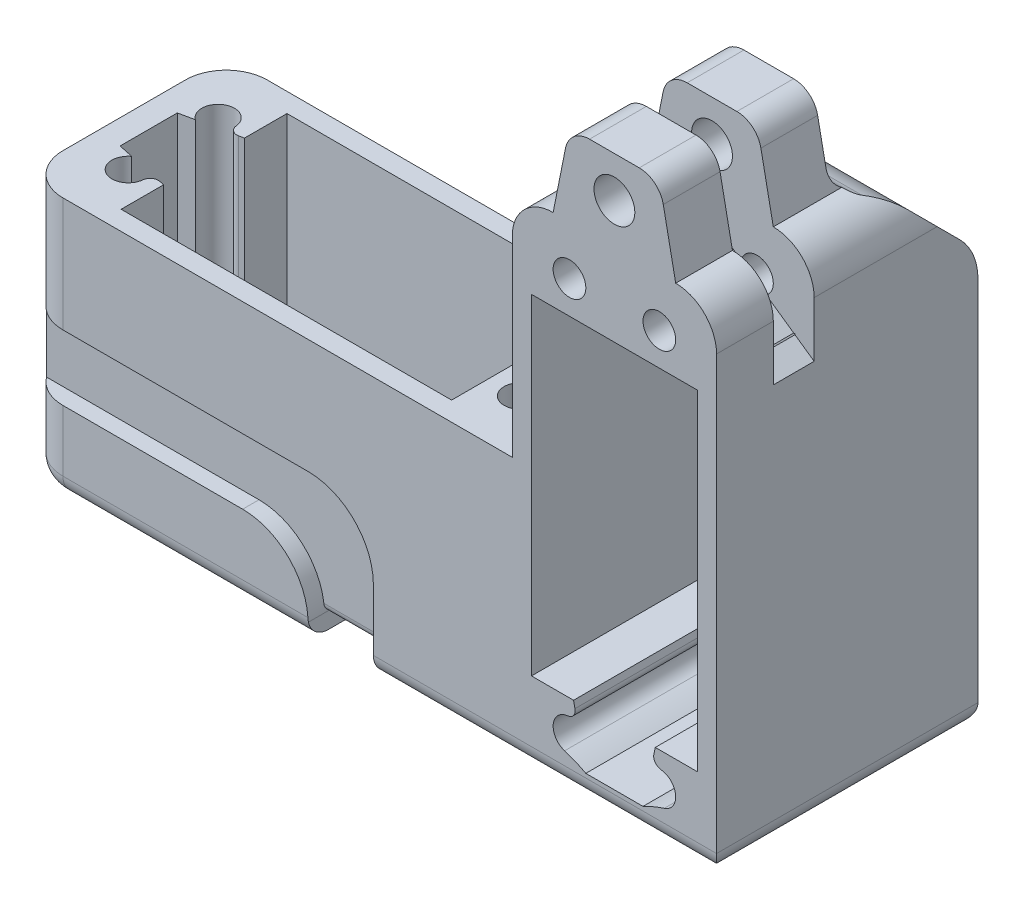
SolidWorks part; units mm, degrees
note: The reader was unsure of these and kept them because the rebuilt part matched: shared geometry of "Croquis3<2>", "Croquis9<3>".
ref_plane "Alzado" through (0, 0, 0) normal (0, 0, 1) x (1, 0, 0)
ref_plane "Planta" through (0, 0, 0) normal (0, 1, 0) x (1, 0, 0)
ref_plane "Vista lateral" through (0, 0, 0) normal (1, 0, 0) x (0, 0, -1)
sketch "Croquis1" plane through (0, 0, 0) normal (0, 0, 1) x (1, 0, 0)
  line L0 (-10, 40) -> (-10, 0) construction
  line L3 (-20, 40) -> (20, 40) construction
  line L4 (-20, 40) -> (-20, 0) construction
  line L5 (-20, 0) -> (20, 0) construction
  line L6 (20, 40) -> (20, 0) construction
  line L7 (-27, 28) -> (-27, 30.5) construction
  line L8 (-27, 30.5) -> (-20, 30.5) construction
  line L9 (-27, 28) -> (-20, 28) construction
  line L10 (27, 28) -> (27, 30.5) construction
  line L11 (27, 30.5) -> (20, 30.5) construction
  line L12 (27, 28) -> (20, 28) construction
  line L13 (-14.4, 40) -> (-14.4, 43.2) construction
  line L14 (-14.4, 43.2) -> (-5.6, 43.2) construction
  line L15 (-5.6, 43.2) -> (-5.6, 40) construction
  line L16 (-14.4, 43.2) -> (-20, 43.2) construction
  line L17 (-20, 43.2) -> (-20, 45.5) construction
  line L18 (-20, 45.5) -> (0, 45.5) construction
  line L19 (0, 45.5) -> (0, 43.2) construction
  line L20 (0, 43.2) -> (-5.6, 43.2) construction
  point P0 (0, 0)
  point P20 (-10, 43.2)
  point P27 (-10, 45.5)
  dimension "D1" = 40
  dimension "D2" = 40
  dimension "D4" = 10
  dimension "D5" = 7
  dimension "D6" = 2.5
  dimension "D7" = 9.5
  dimension "D9" = 8.8
  dimension "D10" = 20
  dimension "D11" = 2.3
  dimension "D12" = 3.2
sketch "Croquis2" plane through (0, 0, 0) normal (0, 1, 0) x (1, 0, 0)
  line L1 (-20, 10) -> (-27, 10) construction
  line L2 (-20, 10) -> (-20, -10) construction
  line L3 (-20, -10) -> (-27, -10) construction
  line L4 (-27, 10) -> (-27, -10) construction
  line L8 (-27, 10.15) -> (-20, 10.15) construction
  line L9 (-20, 10.15) -> (-20, 10) construction
  line L10 (-27, 10.15) -> (-27, 10) construction
  line L11 (-55, 0) -> (55, 0) construction
  line L12 (-20, -10.15) -> (-20, -10) construction
  line L13 (-27, -10.15) -> (-20, -10.15) construction
  line L14 (-27, -10.15) -> (-27, -10) construction
  circle A0 centre (-24, 5.5) radius 2 construction
  point P4 (-20, 0)
  dimension "D4" = 4
  dimension "D1" = 20
  dimension "D2" = 7
  dimension "D3" = 3
  dimension "D5" = 4.5
  dimension "D6" = 0.15
sketch "Croquis3" plane through (0, 0, 0) normal (0, 1, 0) x (1, 0, 0)
  line L1 (-20, -12.5) -> (-25, -12.5)
  line L3 (-20, 12.5) -> (-25, 12.5)
  line L4 (-30, -7.5) -> (-30, 7.5)
  line L5 (-20, 12.5) -> (20, 12.5)
  line L6 (-20, -12.5) -> (20, -12.5)
  line L7 (-20.225, 10.15) -> (20.225, 10.15)
  line L8 (-20.225, -10.15) -> (20.225, -10.15)
  line L9 (-20.225, 10.15) -> (-20.225, -10.15)
  line L10 (-55, 0) -> (55, 0) construction
  line L11 (0, -55) -> (0, 55) construction
  line L12 (-20, 10) -> (-20, -10) construction
  line L13 (20.225, 10.15) -> (20.225, -10.15)
  line L15 (20, 12.5) -> (25, 12.5)
  line L16 (20, -12.5) -> (25, -12.5)
  line L17 (-27, 10.15) -> (-20, 10.15) construction
  line L18 (-27, -10.15) -> (-20, -10.15) construction
  line L19 (25, 12.5) -> (30, 12.5)
  line L20 (30, 12.5) -> (30, -12.5)
  line L21 (30, -12.5) -> (25, -12.5)
  arc A0 (-25, -12.5) -> (-30, -7.5) centre (-25, -7.5) cw
  arc A1 (-30, 7.5) -> (-25, 12.5) centre (-25, 7.5) cw
  circle A2 centre (-24, 5.5) radius 2 construction
  circle A3 centre (-24, 5.5) radius 2
  circle A4 centre (-24, -5.5) radius 2
  circle A5 centre (24, -5.5) radius 2
  circle A6 centre (24, 5.5) radius 2
  point P6 (-30, 0)
  point P9 (30, 12.5)
  point P10 (0, 12.5)
  point P11 (0, -12.5)
  point P14 (0, 10.15)
  point P20 (-30, -12.5)
  point P23 (-30, 12.5)
  point P47 (0, -10.15)
  point P48 (30, -12.5)
  dimension "D3" = 5
  dimension "D1" = 10
  dimension "D2" = 25
  dimension "D4" = 0.225
  dimension "D5" = 0.225
extrude "Saliente-Extruir1" add sketch "Croquis3" along normal up to vertex (28 mm away) up to point (-20, 28, 0)
extrude "Saliente-Extruir2" add sketch "Croquis3<2>" against normal blind 4
sketch "Croquis3<2>" plane through (0, 0, 0) normal (0, 1, 0) x (1, 0, 0) same geometry as "Croquis3"
sketch "Croquis4" plane through (0, 28, 0) normal (0, 1, 0) x (1, 0, 0)
  line L0 (-20, 5) -> (-20, -5)
  line L1 (-20, 10) -> (-20, -10) construction
  line L2 (-20, -5) -> (-27, -3.5)
  line L3 (-27, -3.5) -> (-27, 3.5)
  line L4 (-27, 3.5) -> (-20, 5)
  point P4 (-20, 0)
  dimension "D1" = 7
  dimension "D2" = 10
  dimension "D3" = 7
extrude "Cortar-Extruir1" cut sketch "Croquis4" against normal offset from surface (23 mm away) 5 up to face at (0, 0, 0)
fillet "Redondeo12" radius 1 2 edges at (-22.2588, 16.5, 4.516) (-22.2588, 16.5, -4.516)
sketch "Croquis5" plane through (-20.225, 0, 0) normal (1, 0, 0) x (0, 0, -1)
  line L0 (4.9518, 5) -> (-4.9518, 5) construction
  line L1 (-4.9518, 5) -> (4.9518, 5)
  line L2 (-4.9518, 5) -> (-4.9518, 9)
  line L3 (-4.9518, 9) -> (4.9518, 9)
  line L4 (4.9518, 5) -> (4.9518, 9)
  dimension "D1" = 4
extrude "Cortar-Extruir2" cut sketch "Croquis5" against normal through all
sketch "Croquis6" plane through (0, -4, 0) normal (0, -1, 0) x (1, 0, 0)
  line L0 (-20, 0) -> (0, 0) construction
  circle A0 centre (-10, 0) radius 8.125
  dimension "D1" = 16.25
extrude "Cortar-Extruir3" cut sketch "Croquis6" against normal blind 4
fillet "Redondeo4" radius 5 1 edges at (-27, 9, 0)
sketch3d "Croquis3D4"
  point P0 (30, 6.8279, 1.7662)
ref_plane "Plano1" through (30, 0, 0) normal (1, 0, 0) x (0, 1, 0)
sketch "Croquis7" plane through (30, 0, 0) normal (1, 0, 0) x (0, 1, 0)
  line L0 (16, 24.5) -> (16, -15.5) construction
  line L3 (6, 24.5) -> (46, 24.5) construction
  line L4 (6, 24.5) -> (6, -15.5) construction
  line L5 (6, -15.5) -> (46, -15.5) construction
  line L6 (46, 24.5) -> (46, -15.5) construction
  line L7 (-1, 12.5) -> (-1, 15) construction
  line L8 (-1, 15) -> (6, 15) construction
  line L9 (-1, 12.5) -> (6, 12.5) construction
  line L10 (53, 12.5) -> (53, 15) construction
  line L11 (53, 15) -> (46, 15) construction
  line L12 (53, 12.5) -> (46, 12.5) construction
  line L13 (11.6, 24.5) -> (11.6, 27.7) construction
  line L14 (11.6, 27.7) -> (20.4, 27.7) construction
  line L15 (20.4, 27.7) -> (20.4, 24.5) construction
  line L16 (11.6, 27.7) -> (6, 27.7) construction
  line L17 (6, 27.7) -> (6, 30) construction
  line L18 (6, 30) -> (26, 30) construction
  line L19 (26, 30) -> (26, 27.7) construction
  line L20 (26, 27.7) -> (20.4, 27.7) construction
  point P20 (16, 27.7)
  point P27 (16, 30)
  dimension "D1" = 40
  dimension "D2" = 40
  dimension "D3" = 1
  dimension "D4" = 10
  dimension "D5" = 7
  dimension "D6" = 2.5
  dimension "D7" = 9.5
  dimension "D8" = 24.5
  dimension "D9" = 8.8
  dimension "D10" = 20
  dimension "D11" = 2.3
  dimension "D12" = 3.2
sketch3d "Croquis3D5"
  point P0 (-4.4818, 17.5523, 12.5)
ref_plane "Plano2" through (0, 0, 12.5) normal (0, 0, 1) x (0, 1, 0)
sketch "Croquis9" plane through (0, 0, 12.5) normal (0, 0, 1) x (0, 1, 0)
  line L0 (6, -55) -> (1, -55)
  line L1 (6, -55) -> (6, -30) construction
  line L2 (6, -30) -> (1, -30)
  line L3 (-4, -50) -> (-4, -35)
  line L4 (6, -30) -> (46.45, -30)
  line L5 (6, -55) -> (46.45, -55)
  line L6 (6, -32.35) -> (46.45, -32.35)
  line L7 (6, -52.65) -> (46.45, -52.65)
  line L8 (6, -32.35) -> (6, -52.65)
  line L9 (-4, -35) -> (-4, -30)
  line L10 (26.225, -60.6027) -> (26.225, -26.5509) construction
  line L11 (46.45, -55) -> (51.45, -55)
  line L12 (46.45, -30) -> (51.45, -30)
  line L13 (56.45, -50) -> (56.45, -35)
  line L14 (46.45, -32.35) -> (46.45, -52.65)
  line L15 (28, -30) -> (-4, -30) construction
  line L16 (-4, -30) -> (1, -30)
  line L17 (-4, -50) -> (-4, -55)
  line L18 (-4, -55) -> (1, -55)
  circle A2 centre (2, -37) radius 2
  circle A3 centre (2, -48) radius 2
  arc A4 (51.45, -55) -> (56.45, -50) centre (51.45, -50) ccw
  arc A5 (56.45, -35) -> (51.45, -30) centre (51.45, -35) ccw
  circle A6 centre (50.45, -48) radius 2
  circle A7 centre (50.45, -37) radius 2
  point P4 (6, -42.5)
  point P6 (26.225, -55)
  point P23 (6, -42.5)
  point P24 (-4, -42.5)
  dimension "D1" = 5
  dimension "D9" = 4
  dimension "D2" = 11
  dimension "D3" = 5.5
  dimension "D4" = 20.3
  dimension "D5" = 40.45
  dimension "D6" = 25
  dimension "D7" = 10
  dimension "D8" = 4
  dimension "D10" = 15
  dimension "D11" = 5
extrude "Saliente-Extruir3" add sketch "Croquis9" against normal up to vertex (28 mm away) from vertex at 0 up to point (30, 6, -15.5) starting at point (30, 6, 12.5)
extrude "Saliente-Extruir4" add sketch "Croquis9<3>" against normal blind 4 from surface at -28 contours L14 L6 L8 L7 | L13 A5 L12 L4 L2 L16 L9 L3 L17 L18 L0 L5 L11 A4 L6 L14 L7 L8 A2 A3 A6 A7 | A7 | A6 | A2 | A3 starting at face at (35, 50.45, -15.5)
sketch "Croquis9<3>" plane through (0, 0, 12.5) normal (0, 0, 1) x (0, 1, 0) same geometry as "Croquis9"
sketch "Croquis10" plane through (0, 0, -19.5) normal (0, 0, -1) x (-1, 0, 0)
  line L0 (-50, 56.45) -> (-35, 56.45) construction
  circle A0 centre (-42.5, 16) radius 8.125
  point P8 (-42.5, 56.45)
  dimension "D1" = 16.25
extrude "Cortar-Extruir4" cut sketch "Croquis10" against normal through all contours A0
sketch "Croquis12" plane through (0, 0, 12.5) normal (0, 0, 1) x (1, 0, 0)
  line L4 (47.5, 6) -> (37.5, 6)
  line L5 (32.35, 6) -> (52.65, 6) construction
  line L6 (32.35, 6) -> (52.65, 6) construction
  line L7 (39, -1) -> (46, -1)
  line L8 (37.5, 6) -> (39, -1)
  line L9 (46, -1) -> (47.5, 6)
  point P11 (42.5, 6)
  point P12 (42.5, -1)
  point P13 (42.5, 6)
  dimension "D4" = 10
  dimension "D5" = 7
  dimension "D6" = 7
extrude "Cortar-Extruir5" cut sketch "Croquis12" against normal offset from surface (23 mm away) 5 up to face at (50.625, 16, -15.5)
fillet "Redondeo10" radius 15 2 edges at (38.6111, 0.8149, 1) (46.3889, 0.8149, 1)
fillet "Redondeo11" radius 1 2 edges at (47.016, 3.7412, 1) (37.984, 3.7412, 1)
sketch "Croquis13" plane through (0, 6, 0) normal (0, 1, 0) x (1, 0, 0)
  line L1 (37.5, 10.5) -> (47.5, 10.5)
  line L2 (37.5, 10.5) -> (37.5, 6.5)
  line L3 (37.5, 6.5) -> (47.5, 6.5)
  line L4 (47.5, 10.5) -> (47.5, 6.5)
  dimension "D1" = 4
extrude "Cortar-Extruir6" cut sketch "Croquis13" against normal through all
fillet "Redondeo15" radius 5 1 edges at (30, 12, -12.5)
fillet "Redondeo16" radius 2.5 8 edges at (15, -4, 12.5) (-28.5355, -4, 11.0355) (-30, -4, 0) (-28.5355, -4, -11.0355) (28.5355, -4, -13.9645) (55, -4, -3.5) (42.5, -4, -19.5) (0, -4, -12.5)
sketch "Croquis14" plane through (0, -4, 0) normal (0, -1, 0) x (1, 0, 0)
  line L0 (47.5, -6.5) -> (47.5, 5.5)
  line L1 (37.5, -6.5) -> (37.5, -2.5)
  line L2 (37.5, -2.5) -> (5, -2.5)
  line L3 (5, -2.5) -> (5, 12.5)
  line L4 (-25, 12.5) -> (55, 12.5) construction
  line L5 (13, 12.5) -> (13, 5.5)
  line L6 (13, 5.5) -> (47.5, 5.5)
  line L7 (5, 12.5) -> (13, 12.5)
  line L8 (37.5, -6.5) -> (47.5, -6.5)
  dimension "D1" = 8
  dimension "D2" = 4
  dimension "D3" = 8
  dimension "D4" = 5
extrude "Cortar-Extruir7" cut sketch "Croquis14" against normal blind 2
sketch "Croquis15" plane through (0, 0, 0) normal (0, 0, 1) x (1, 0, 0)
  line L0 (5, -4) -> (5, 6)
  line L1 (5, 6) -> (-30, 6)
  line L2 (-30, 28) -> (-30, -1.5) construction
  line L3 (13, -4) -> (13, 14)
  line L4 (13, 14) -> (-30, 14)
  line L5 (-30, 14) -> (-30, 6)
  line L6 (5, -4) -> (13, -4)
  dimension "D1" = 8
  dimension "D2" = 10
extrude "Cortar-Extruir8" cut sketch "Croquis15" against normal blind 2 from surface at 12.5 starting at face at (25.625, 33.8589, 12.5)
fillet "Redondeo17" radius 1 1 edges at (9, -2, 10.5)
fillet "Redondeo18" radius 8 5 edges at (47.5, -3, 5.5) (37.5, -3, -2.5) (5, -3, -2.5) (5, 6, 11.5) (13, 14, 11.5)
fillet "Redondeo19" radius 2 1 edges at (13, -3, 5.5)
sketch "Croquis17" plane through (55, 0, 0) normal (1, 0, 0) x (0, 0, -1)
  line L0 (19.5, 56.45) -> (19.5, 46.45)
  line L1 (19.5, -1.5) -> (19.5, 51.45) construction
  line L2 (19.5, 46.45) -> (9.5, 56.45)
  line L3 (19.5, 56.45) -> (-12.5, 56.45) construction
  line L4 (9.5, 56.45) -> (19.5, 56.45)
  dimension "D1" = 10
extrude "Cortar-Extruir9" cut sketch "Croquis17" against normal through all both and the other way through all
fillet "Redondeo21" radius 7.5 2 edges at (42.5, 46.45, -19.5) (42.5, 56.45, -9.5)
sketch "Croquis18" plane through (0, 0, 12.5) normal (0, 0, 1) x (1, 0, 0)
  line L0 (50, 56.45) -> (35, 56.45) construction
  line L1 (50, 56.45) -> (35, 56.45)
  line L2 (35, 56.45) -> (37, 66.45)
  line L3 (37, 66.45) -> (48, 66.45)
  line L4 (48, 66.45) -> (50, 56.45)
  circle A0 centre (42.5, 61.45) radius 2.5
  point P2 (42.5, 66.45)
  point P5 (42.5, 56.45)
  point P10 (36, 61.45)
  dimension "D3" = 5
  dimension "D1" = 10
  dimension "D2" = 11
extrude "Saliente-Extruir5" add sketch "Croquis18" against normal up to vertex (18.8934 mm away)
fillet "Redondeo22" radius 3 3 edges at (42.5, 56.45, -6.3934) (37, 66.45, 3.0533) (48, 66.45, 3.0533)
ref_plane "Plano3" through (0, 0, 3.0533) normal (0, 0, 1) x (1, 0, 0)
sketch "Croquis19" plane through (0, 0, 3.0533) normal (0, 0, 1) x (1, 0, 0)
  line L1 (55, 44.6974) -> (55, 69.45)
  line L2 (55, 69.45) -> (42.5, 69.45)
  line L3 (55, -1.5) -> (55, 51.45) construction
  line L4 (42.5, 53.45) -> (55, 44.6974)
  arc A0 (42.5, 69.45) -> (42.5, 53.45) centre (42.5, 61.45) ccw
  dimension "D1" = 16
  dimension "D2" = 55
extrude "Cortar-Extruir10" cut sketch "Croquis19" against normal mid plane 5
sketch "Croquis20" plane through (0, 0, 0) normal (0, 0, 1) x (1, 0, 0)
  line L0 (-30, 28) -> (-30, -1.5) construction
  line L1 (-30, 0) -> (30, 0)
  line L2 (-30, 0) -> (-30, 28)
  line L3 (-30, 28) -> (30, 28)
  line L4 (55, -4) -> (55, 66.45)
  line L6 (55, -1.5) -> (55, 51.45) construction
  line L8 (30, 28) -> (30, 66.45)
  line L9 (30, 66.45) -> (55, 66.45)
  line L10 (30, 51.45) -> (30, 28) construction
  line L11 (45.5406, 66.45) -> (39.4594, 66.45) construction
  line L12 (5, -4) -> (-25, -4) construction
  line L13 (-25, 28) -> (30, 28) construction
  line L14 (30, 0) -> (30, -4)
  line L15 (52.5, -4) -> (13, -4) construction
  line L16 (30, -4) -> (55, -4)
  dimension "D1" = 4
